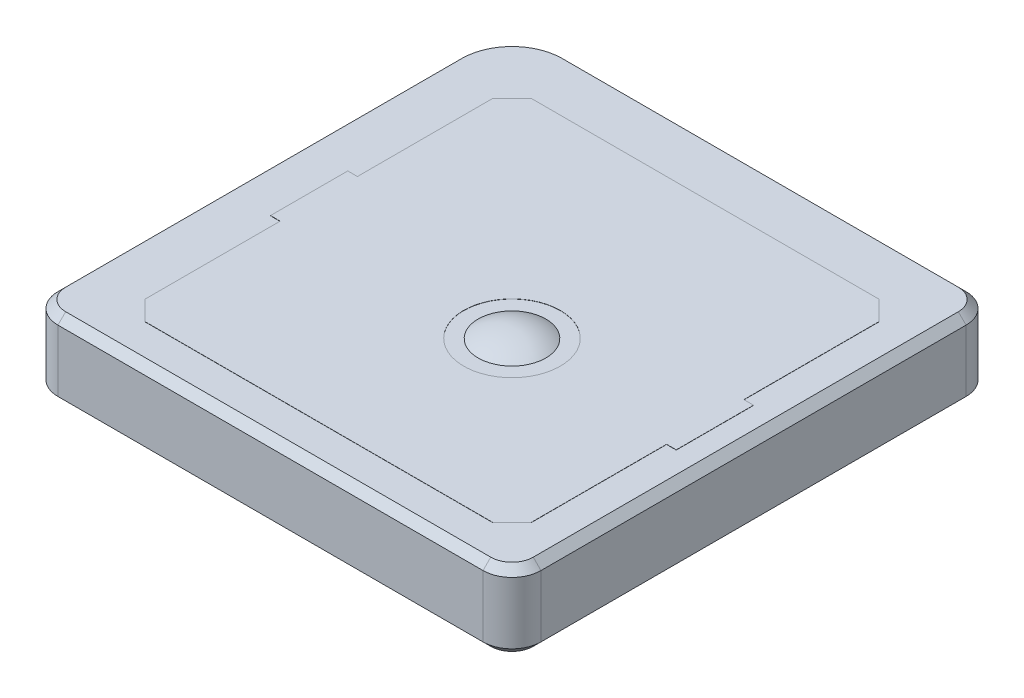
SolidWorks part; units mm, degrees
ref_plane "Front Plane" through (0, 0, 0) normal (0, 0, 1) x (1, 0, 0)
ref_plane "Top Plane" through (0, 0, 0) normal (0, 1, 0) x (1, 0, 0)
ref_plane "Right Plane" through (0, 0, 0) normal (1, 0, 0) x (0, 0, -1)
sketch "Sketch1" plane through (0, 0, 0) normal (0, 1, 0) x (1, 0, 0)
  line L1 (-12.75, -10.75) -> (9.25, -10.75)
  line L2 (-14.25, -9.25) -> (-14.25, 11.25)
  line L3 (-11.25, 14.25) -> (9.25, 14.25)
  line L4 (10.75, -9.25) -> (10.75, 12.75)
  line L5 (-14.25, -10.75) -> (10.75, 14.25) construction
  line L6 (-14.25, 14.25) -> (10.75, -10.75) construction
  arc A0 (-14.25, 11.25) -> (-11.25, 14.25) centre (-11.25, 11.25) cw
  arc A1 (9.25, 14.25) -> (10.75, 12.75) centre (9.25, 12.75) cw
  arc A2 (10.75, -9.25) -> (9.25, -10.75) centre (9.25, -9.25) cw
  arc A3 (-12.75, -10.75) -> (-14.25, -9.25) centre (-12.75, -9.25) cw
  point P0 (-1.75, 1.75)
  dimension "D5" = 3
  dimension "D6" = 1.5
  dimension "D1" = 25
  dimension "D2" = 25
  dimension "D3" = 1.75
  dimension "D4" = 1.75
extrude "Boss-Extrude1" add sketch "Sketch1" along normal blind 4
chamfer "Chamfer1" distance 0.4 angle 45 16 edges at (-14.25, 0, -1) (-13.8107, 0, 10.3107) (-1.75, 0, 10.75) (10.3107, 0, 10.3107) (10.75, 0, -1.75) (10.3107, 0, -13.8107) (-1, 0, -14.25) (-13.3713, 0, -13.3713) (-1, 4, -14.25) (10.3107, 4, -13.8107) (10.75, 4, -1.75) (10.3107, 4, 10.3107) (-1.75, 4, 10.75) (-13.8107, 4, 10.3107) (-14.25, 4, -1) (-13.3713, 4, -13.3713)
sketch "Sketch2" plane through (0, 0, 0) normal (0, 0, 1) x (1, 0, 0)
  line L0 (0, 5.8921) -> (0, -4.4343) construction
  line L1 (-12.75, 4) -> (9.25, 4) construction
  line L2 (-3.2153, 1.9839) -> (-0.5, 1.9839)
  line L3 (-0.5, 1.9839) -> (-0.5, -2.4)
  line L4 (-0.5, -2.4) -> (0, -2.4)
  line L5 (9.25, 0) -> (-12.75, 0) construction
  line L6 (0, -2.4) -> (0, 4.5)
  arc A1 (0, 4.5) -> (-3.2153, 1.9839) centre (0, 1.1875) ccw
  point P5 (0, 4.5)
  point P6 (0, 4)
  point P7 (1.75, 4)
  point P10 (-1.75, 4)
  dimension "D1" = 0.5
  dimension "D2" = 3.5
  dimension "D3" = 0.5
  dimension "D4" = 2.4
revolve "Revolve1" add sketch "Sketch2" angle 360 about L0
sketch "Sketch3" plane through (0, 0, 0) normal (0, 1, 0) x (1, 0, 0)
  line L0 (-14.25, -9.25) -> (-14.25, 11.25) construction
  line L1 (-10.25, 11.25) -> (7.75, 11.25)
  line L2 (-11.25, 10.25) -> (-11.25, 3.25)
  line L3 (-10.25, -8.75) -> (7.75, -8.75)
  line L4 (8.75, 10.25) -> (8.75, 3.25)
  line L5 (-11.25, 14.25) -> (9.25, 14.25) construction
  line L6 (-11.25, 10.25) -> (-10.25, 11.25)
  line L7 (-11.25, -7.75) -> (-10.25, -8.75)
  line L8 (7.75, -8.75) -> (8.75, -7.75)
  line L9 (7.75, 11.25) -> (8.75, 10.25)
  line L10 (-11.25, 3.25) -> (-11.75, 3.25)
  line L11 (-11.75, 3.25) -> (-11.75, -0.75)
  line L12 (-11.75, -0.75) -> (-11.25, -0.75)
  line L13 (-11.25, -0.75) -> (-11.25, -7.75)
  line L14 (8.75, 3.25) -> (9.25, 3.25)
  line L15 (9.25, 3.25) -> (9.25, -0.75)
  line L16 (9.25, -0.75) -> (8.75, -0.75)
  line L17 (8.75, -0.75) -> (8.75, -7.75)
  circle A0 centre (0, 0) radius 2.5
  point P0 (-11.25, 11.25)
  point P1 (8.75, -8.75)
  point P2 (-11.25, -8.75)
  point P3 (8.75, 11.25)
  dimension "D5" = 5
  dimension "D1" = 20
  dimension "D2" = 20
  dimension "D3" = 3
  dimension "D4" = 3
  dimension "D6" = 4
  dimension "D11" = 0.5
  dimension "D12" = 0.5
  dimension "D13" = 4
extrude "Boss-Extrude2" add sketch "Sketch3" along normal blind 0.01 from surface starting at face at (0, 4, -1.75)
